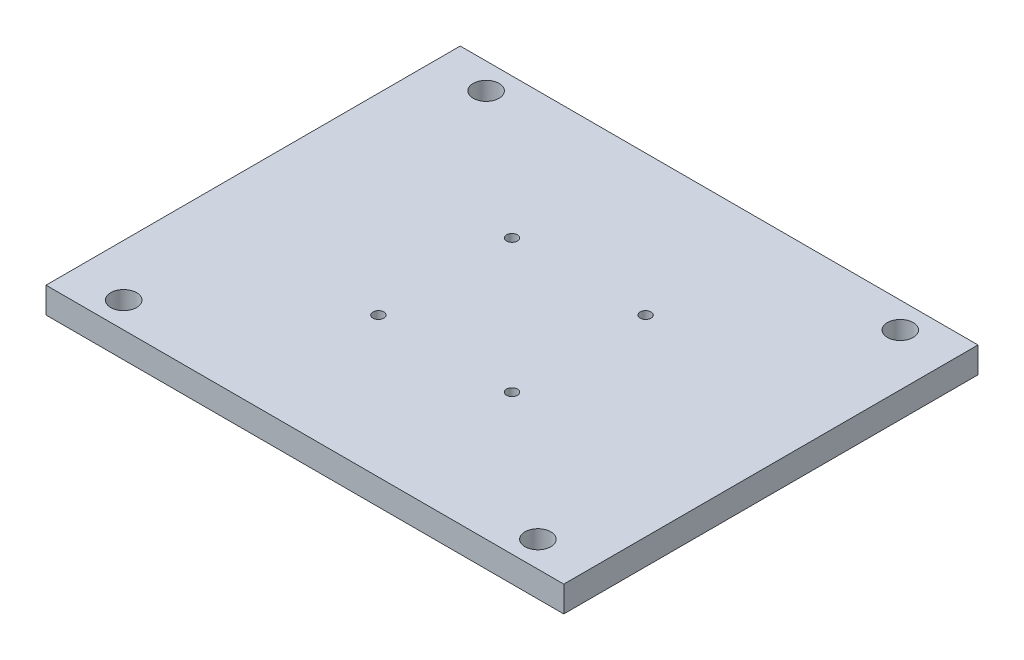
SolidWorks part; units mm, degrees
ref_plane "Front Plane" through (0, 0, 0) normal (0, 0, 1) x (1, 0, 0)
ref_plane "Top Plane" through (0, 0, 0) normal (0, 1, 0) x (1, 0, 0)
ref_plane "Right Plane" through (0, 0, 0) normal (1, 0, 0) x (0, 0, -1)
sketch "Sketch1" plane through (0, 0, 0) normal (0, 1, 0) x (1, 0, 0)
  line L1 (0, 0) -> (200, 0)
  line L2 (0, 0) -> (0, 160)
  line L3 (0, 160) -> (200, 160)
  line L4 (200, 0) -> (200, 160)
  dimension "D1" = 160
  dimension "D2" = 200
extrude "Boss-Extrude1" add sketch "Sketch1" along normal blind 5 and the other way blind 5
sketch "Sketch2" plane through (0, 5, 0) normal (0, 1, 0) x (1, 0, 0)
  line L0 (200, 160) -> (0, 160) construction
  line L2 (200, 0) -> (200, 160) construction
  line L3 (0, 0) -> (200, 0) construction
  line L4 (0, 160) -> (0, 0) construction
  circle A0 centre (180, 150) radius 5
  circle A1 centre (74.1977, 105.8023) radius 2.1
  circle A2 centre (74.1977, 54.1977) radius 2.1
  circle A3 centre (125.8023, 54.1977) radius 2.1
  circle A4 centre (125.8023, 105.8023) radius 2.1
  circle A5 centre (180, 10) radius 5
  circle A6 centre (20, 10) radius 5
  circle A7 centre (20, 150) radius 5
  point P8 (180, 150)
  point P9 (125.8023, 105.8023)
  point P10 (74.1977, 105.8023)
  point P11 (74.1977, 54.1977)
  point P12 (125.8023, 54.1977)
  point P21 (100, 80)
  point P22 (180, 10)
  point P23 (20, 10)
  point P24 (20, 150)
  dimension "D1" = 10
  dimension "D2" = 20
  dimension "D3" = 10
  dimension "D4" = 20
  dimension "D5" = 20
  dimension "D6" = 10
  dimension "D7" = 20
  dimension "D8" = 10
extrude "Cut-Extrude1" cut sketch "Sketch2" against normal through all
